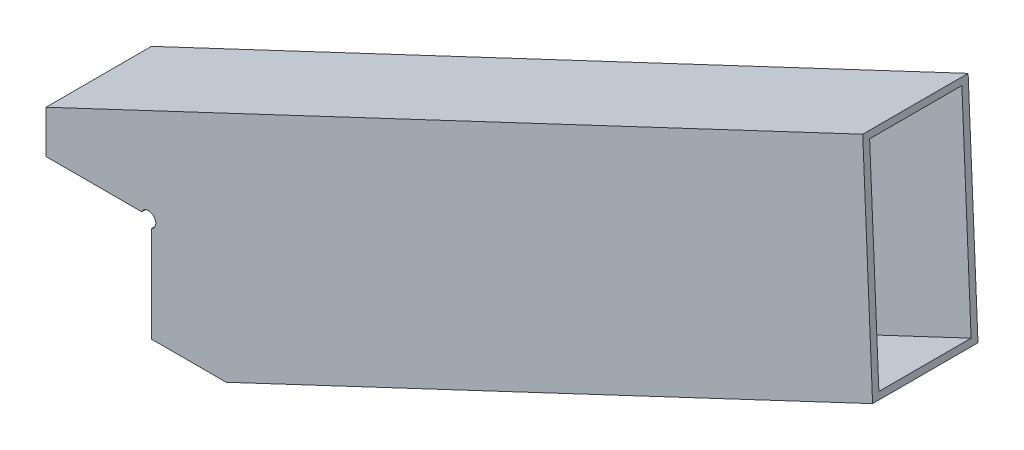
SolidWorks part; units mm, degrees
material "PET"
ref_plane "Front" through (0, 0, 0) normal (0, 0, 1) x (1, 0, 0)
ref_plane "Top" through (0, 0, 0) normal (0, 1, 0) x (1, 0, 0)
ref_plane "Right" through (0, 0, 0) normal (1, 0, 0) x (0, 0, -1)
sketch "Sketch1" plane through (0, 0, 0) normal (0, 0, 1) x (1, 0, 0)
  line L0 (184.6516, -101.6445) -> (174.5844, 131.6406) construction
  line L1 (0, 0) -> (-50.8, 0) construction
  line L2 (0, 0) -> (0, 25.4) construction
  line L3 (0, 25.4) -> (-50.8, 25.4) construction
  line L4 (-50.8, 0) -> (-50.8, 25.4) construction
  line L5 (184.6516, -101.6445) -> (210.0516, -101.6445) construction
  line L6 (174.5844, 131.6406) -> (-22.225, 38.8695)
  line L7 (176.9597, 76.5993) -> (21.1934, 3.175)
  line L9 (174.5844, 131.6406) -> (176.9597, 76.5993)
  line L11 (3.175, 3.175) -> (3.175, 28.575)
  line L12 (3.175, 28.575) -> (-22.225, 28.575) construction
  line L15 (-22.225, 28.575) -> (3.175, 28.575)
  line L16 (-50.8, 25.4) -> (-44.0644, 28.575) construction
  line L17 (-22.225, 38.8695) -> (-22.225, 28.575)
  line L18 (3.175, 3.175) -> (21.1934, 3.175)
  dimension "D1" = 50.8
  dimension "D2" = 25.4
  dimension "D3" = 92.471
  dimension "D4" = 106.2406
  dimension "D6" = 25.4
  dimension "D7" = 233.5022
  dimension "D8" = 50.8
  dimension "D9" = 67.233
  dimension "D10" = 249.169
  dimension "D11" = 3.175
  dimension "D12" = 3.175
  dimension "D13" = 25.4
  dimension "D14" = 25.4
  dimension "D15" = 184.6516
extrude "Boss-Extrude1" add sketch "Sketch1" along normal blind 25.4
shell "Shell1" thickness 1.5875 removed face at (-9.525, 28.575, 12.7) removed face at (3.175, 15.875, 12.7) removed face at (175.7721, 104.12, 12.7) removed face at (12.1842, 3.175, 12.7) removed face at (-22.225, 33.7223, 12.7)
sketch "Sketch2" plane through (0, 0, 25.4) normal (0, 0, 1) x (1, 0, 0)
  line L0 (2.4613, 27.8613) -> (3.175, 28.575) construction
  line L2 (-22.225, 28.575) -> (3.175, 28.575) construction
  line L4 (3.175, 28.575) -> (3.175, 3.175) construction
  line L5 (0.8401, 28.575) -> (3.175, 26.2401) construction
  circle A0 centre (2.4613, 27.8613) radius 1.7713
  dimension "D2" = 0.762
  dimension "D3" = 3.302
extrude "Cut-Extrude1" cut sketch "Sketch2" against normal through all
